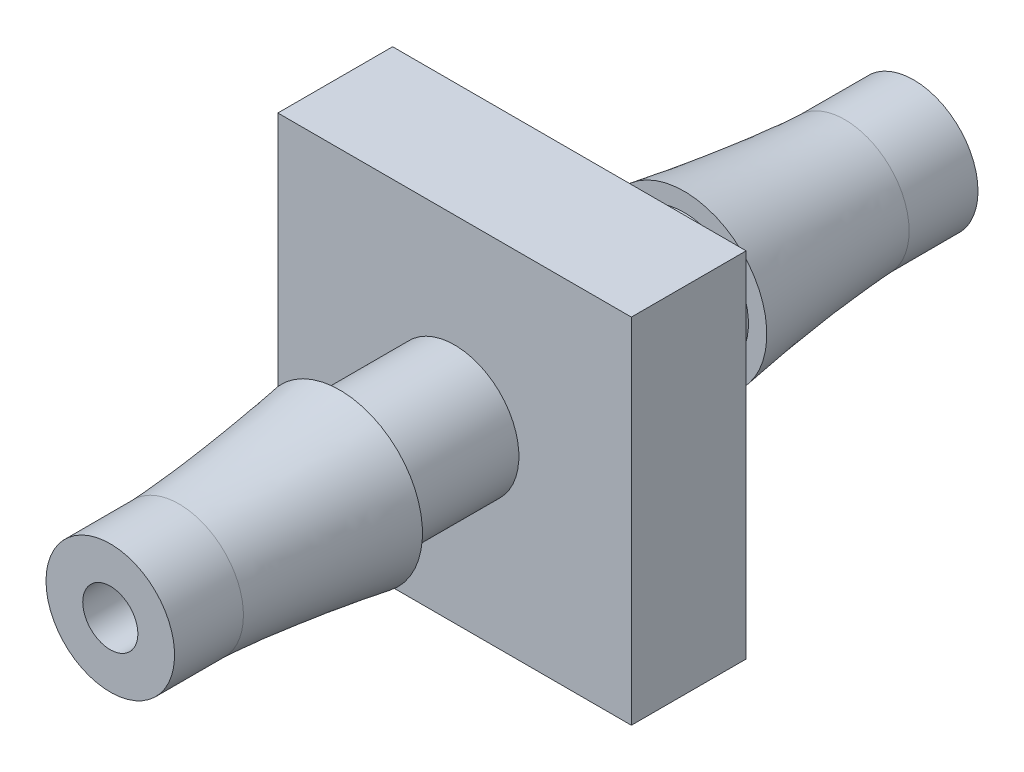
SolidWorks part; units mm, degrees
ref_plane "Alzado" through (0, 0, 0) normal (0, 0, 1) x (1, 0, 0)
ref_plane "Planta" through (0, 0, 0) normal (0, 1, 0) x (1, 0, 0)
ref_plane "Vista lateral" through (0, 0, 0) normal (1, 0, 0) x (0, 0, -1)
sketch "Croquis1" plane through (0, 0, 0) normal (0, 0, 1) x (1, 0, 0)
  line L1 (-3.85, -3.85) -> (3.85, -3.85)
  line L2 (-3.85, -3.85) -> (-3.85, 3.85)
  line L3 (-3.85, 3.85) -> (3.85, 3.85)
  line L4 (3.85, -3.85) -> (3.85, 3.85)
  line L5 (-3.85, -3.85) -> (3.85, 3.85) construction
  line L6 (-3.85, 3.85) -> (3.85, -3.85) construction
  point P0 (0, 0)
  dimension "D1" = 7.7
  dimension "D2" = 7.7
extrude "Saliente-Extruir1" add sketch "Croquis1" along normal blind 2.5
sketch "Croquis2" plane through (0, 0, 0) normal (0, 0, -1) x (-1, 0, 0)
  circle A0 centre (0, 0) radius 1.4
  dimension "D1" = 2.8
extrude "Saliente-Extruir2" add sketch "Croquis2" along normal blind 7.5
ref_plane "Plano1" through (0, 0, -2.5) normal (0, 0, -1) x (-1, 0, 0)
sketch "Croquis3" plane through (0, 0, -2.5) normal (0, 0, -1) x (-1, 0, 0)
  circle A0 centre (0, 0) radius 1.8
  dimension "D1" = 3.6
ref_plane "Plano2" through (0, 0, 1.25) normal (0, 0, -1) x (-1, 0, 0)
ref_plane "Plano3" through (0, 0, -6) normal (0, 0, -1) x (-1, 0, 0)
sketch "Croquis5" plane through (0, 0, -6) normal (0, 0, -1) x (-1, 0, 0)
  circle A0 centre (0, 0) radius 1.4
loft "Recubrir2" add profiles "Croquis3", "Croquis5" connector at (-0.3384, 1.7679, -2.5) connector at (-0.8678, 1.0986, -6)
mirror "Simetría2" about plane through (0, 0, 1.25) normal (0, 0, -1) of "Saliente-Extruir2", "Recubrir2"
sketch "Croquis6" plane through (0, 0, -7.5) normal (0, 0, -1) x (-1, 0, 0)
  circle A0 centre (0, 0) radius 0.6
  dimension "D1" = 1.2
extrude "Cortar-Extruir1" cut sketch "Croquis6" against normal through all
